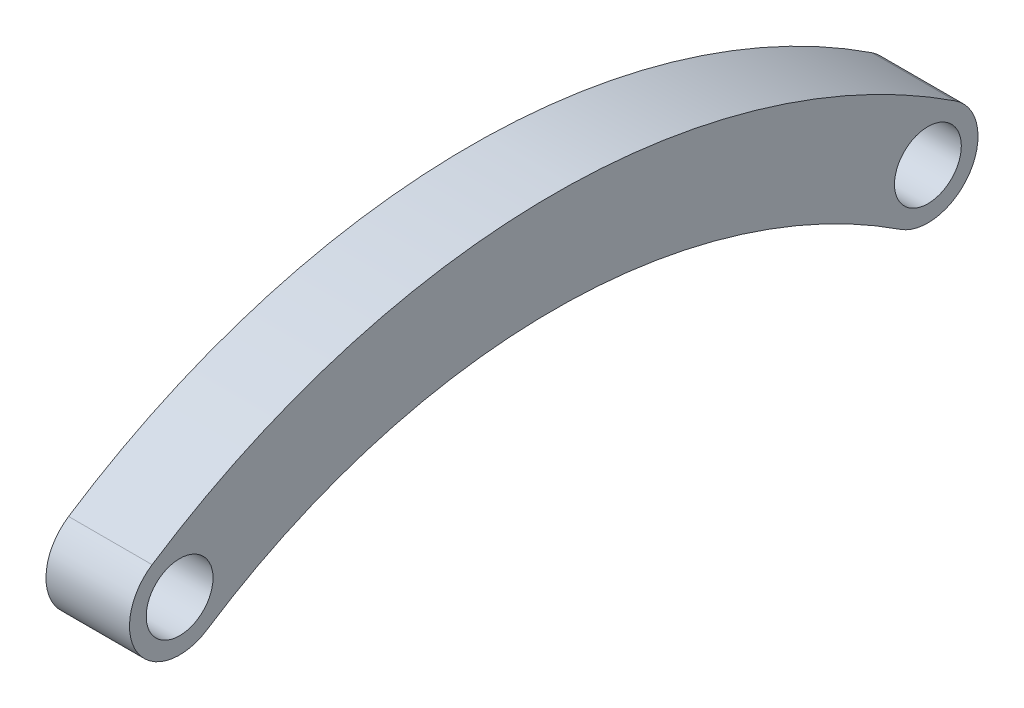
SolidWorks part; units mm, degrees
ref_plane "Front Plane" through (0, 0, 0) normal (0, 0, 1) x (1, 0, 0)
ref_plane "Top Plane" through (0, 0, 0) normal (0, 1, 0) x (1, 0, 0)
ref_plane "Right Plane" through (0, 0, 0) normal (1, 0, 0) x (0, 0, -1)
sketch "Sketch1" plane through (0, 0, 0) normal (1, 0, 0) x (0, 0, -1)
  line L0 (0, 55) -> (0, -55) construction
  line L1 (0, 0) -> (0, 6) construction
  line L2 (-22.4, -6.7) -> (22.4, -6.7) construction
  line L3 (81.1274, 6) -> (-72.2732, 6) construction
  line L4 (-25.4, 29.1562) -> (-25.4, -3.7) construction
  line L5 (25.4, 30.6853) -> (25.4, -3.7) construction
  arc A0 (0, 0) -> (20.7527, -6.2073) centre (0, -37.7948) cw
  arc A1 (0, 6) -> (24.0473, -1.1927) centre (0, -37.7948) cw
  arc A2 (20.7527, -6.2073) -> (24.0473, -1.1927) centre (22.4, -3.7) ccw
  arc A3 (-20.7527, -6.2073) -> (-24.0473, -1.1927) centre (-22.4, -3.7) cw
  arc A4 (0, 6) -> (-24.0473, -1.1927) centre (0, -37.7948) ccw
  arc A5 (0, 0) -> (-20.7527, -6.2073) centre (0, -37.7948) ccw
  circle A6 centre (22.4, -3.7) radius 2 construction
  dimension "D4" = 4
  dimension "D2" = 12.7
  dimension "D3" = 50.8
  dimension "D1" = 6
extrude "Boss-Extrude1" add sketch "Sketch1" along normal mid plane 5
sketch "Sketch2" plane through (2.5, 0, 0) normal (1, 0, 0) x (0, 0, -1)
  line L0 (0, 55) -> (0, -55) construction
  circle A0 centre (-22.4, -3.7) radius 2
  arc A1 (-24.0473, -1.1927) -> (-20.7527, -6.2073) centre (-22.4, -3.7) ccw construction
  circle A2 centre (22.4, -3.7) radius 2
  dimension "D1" = 4
extrude "Cut-Extrude1" cut sketch "Sketch2" against normal up to surface (5 mm away) up to face at (-2.5, -1.1736, 0)
